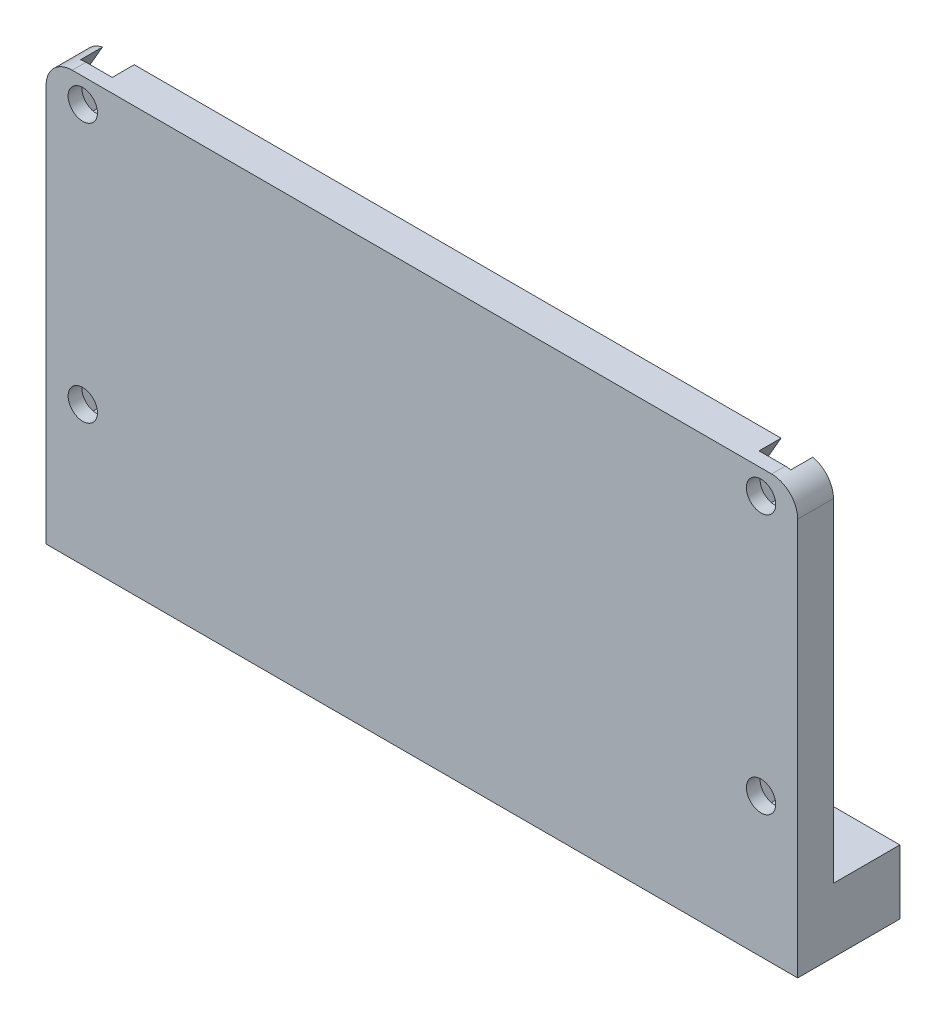
SolidWorks part; units mm, degrees
ref_plane "Front Plane" through (0, 0, 0) normal (0, 0, 1) x (1, 0, 0)
ref_plane "Top Plane" through (0, 0, 0) normal (0, 1, 0) x (1, 0, 0)
ref_plane "Right Plane" through (0, 0, 0) normal (1, 0, 0) x (0, 0, -1)
sketch "Sketch1" plane through (0, 0, 0) normal (0, 0, 1) x (1, 0, 0)
  line L1 (81, 11.6) -> (1, 11.6) construction
  line L3 (0, -35.2) -> (82, -35.2)
  line L5 (79.15, 11.6) -> (2.85, 11.6)
  line L9 (82, -35.2) -> (82, 8.75)
  line L10 (0, 8.75) -> (0, -35.2)
  line L11 (4, 8.9396) -> (4, -41.6656) construction
  circle A0 centre (4, 8.9396) radius 1.6 construction
  circle A1 centre (78, 8.9396) radius 1.6 construction
  circle A2 centre (4, -29.89) radius 1.6 construction
  circle A3 centre (4, 8.9396) radius 1.6
  circle A4 centre (78, 8.9396) radius 1.6
  arc A5 (82, 8.75) -> (79.15, 11.6) centre (79.15, 8.75) ccw
  arc A6 (0, 8.75) -> (2.85, 11.6) centre (2.85, 8.75) cw
  dimension "D1" = 46.8
  dimension "D2" = 2.85
extrude "Boss-Extrude1" add sketch "Sketch1" along normal blind 11.15 contours A3 | L5 A6 L10 L3 L9 A5 | A4 region at (4, 8.9396, 0)
sketch "Sketch2" plane through (0, 0, 0) normal (0, 0, -1) x (-1, 0, 0)
  line L0 (0, -49.6) -> (-82, -49.6) construction
  line L1 (0, -49.6) -> (-82, -49.6) construction
  line L2 (-82, -54.6) -> (0, -54.6)
  line L3 (-82, -34.6) -> (0, -34.6)
  line L4 (-82, -35.2) -> (-82, 8.75) construction
  line L5 (0, 8.75) -> (0, -35.2) construction
  line L7 (0, -34.6) -> (0, -35.2)
  line L8 (-82, -35.2) -> (-82, -34.6)
  line L9 (-82, -35.2) -> (0, -35.2)
  dimension "D1" = 5
  dimension "D2" = 20
extrude "Cut-Extrude1" cut sketch "Sketch2" against normal blind 8 contours L3 L7 L9 L8
sketch "Sketch3" plane through (0, -34.6, 0) normal (0, -1, 0) x (1, 0, 0)
  line L0 (10.85, 4) -> (10.85, 0)
  line L1 (14.15, 4) -> (14.15, 0)
  line L2 (16.75, 4) -> (16.75, 0)
  line L3 (23.25, 4) -> (23.25, 0)
  line L4 (0, 0) -> (82, 0)
  line L5 (82, 0) -> (82, 8)
  line L6 (82, 8) -> (0, 8)
  line L7 (0, 8) -> (0, 0)
  line L8 (10.85, 0) -> (14.15, 0)
  line L9 (82, 0) -> (82, 8)
  line L10 (82, 8) -> (0, 8)
  line L11 (0, 8) -> (0, 0)
  line L12 (25.85, 4) -> (25.85, 0)
  line L13 (29.15, 4) -> (29.15, 0)
  line L14 (25.85, 0) -> (82, 0)
  line L15 (16.75, 0) -> (23.25, 0)
  arc A0 (14.15, 4) -> (10.85, 4) centre (12.5, 4) ccw
  arc A1 (23.25, 4) -> (16.75, 4) centre (20, 4) ccw
  arc A2 (29.15, 4) -> (25.85, 4) centre (27.5, 4) ccw
  line M5 (0, 0) -> (82, 0)
  dimension "D2" = 3.3
  dimension "D3" = 3.3
  dimension "D4" = 15
  dimension "D5" = 7.5
  dimension "D6" = 6.5
  dimension "D7" = 20
  dimension "D1" = 0
extrude "Cut-Extrude2" cut sketch "Sketch3" against normal up to next contours L13 A2 L12 M5 | A0 L0 L8 L1 | A1 L2 L15 L3 region at (27.5, -34.6, 2.6608)
sketch "Sketch4" plane through (0, 11.6, 0) normal (0, 1, 0) x (1, 0, 0)
  line L0 (9.25, -4) -> (9.25, 0)
  line L1 (10.85, 0) -> (2.85, 0) construction
  line L2 (15.75, -4) -> (15.75, 0)
  line L3 (16.75, 0) -> (14.15, 0) construction
  line L4 (15.75, 0) -> (9.25, 0)
  line L5 (24.25, -4) -> (24.25, 0)
  line L6 (25.85, 0) -> (23.25, 0) construction
  line L7 (24.25, 0) -> (30.75, 0)
  line L8 (79.15, 0) -> (29.15, 0) construction
  line L9 (30.75, 0) -> (30.75, -4)
  arc A0 (10.85, -4) -> (14.15, -4) centre (12.5, -4) ccw construction
  arc A1 (25.85, -4) -> (29.15, -4) centre (27.5, -4) ccw construction
  arc A2 (10.85, -4) -> (14.15, -4) centre (12.5, -4) ccw construction
  arc A3 (25.85, -4) -> (29.15, -4) centre (27.5, -4) ccw construction
  arc A4 (9.25, -4) -> (15.75, -4) centre (12.5, -4) ccw
  arc A5 (24.25, -4) -> (30.75, -4) centre (27.5, -4) ccw
  dimension "D1" = 6.5
  dimension "D2" = 6.5
extrude "Cut-Extrude3" cut sketch "Sketch4" against normal offset from surface (40.2 mm away) 6 up to face at (25.25, -34.6, 2.9094)
sketch "Sketch6" plane through (0, 11.6, 0) normal (0, 1, 0) x (1, 0, 0)
  line L0 (15.75, -4) -> (15.75, 0) construction
  line L1 (24.25, 0) -> (24.25, -4) construction
  line L2 (15.75, -4) -> (15.75, 0)
  line L3 (24.25, 0) -> (24.25, -4)
  line L4 (12.5, -7.25) -> (0, -7.25)
  line L5 (0, -11.15) -> (0, 0) construction
  line L6 (0, -7.25) -> (0, 1.0612)
  line L7 (0, 1.0612) -> (15.75, 1.0612)
  line L8 (15.75, 1.0612) -> (15.75, 0)
  line L9 (27.5, -7.25) -> (41, -7.25)
  line L10 (41, -7.25) -> (41, 0)
  line L11 (79.15, 0) -> (30.75, 0) construction
  line L12 (41, 0) -> (24.25, 0)
  arc A0 (9.25, -4) -> (15.75, -4) centre (12.5, -4) ccw construction
  arc A1 (24.25, -4) -> (30.75, -4) centre (27.5, -4) ccw construction
  arc A2 (12.5, -7.25) -> (15.75, -4) centre (12.5, -4) ccw
  arc A3 (24.25, -4) -> (27.5, -7.25) centre (27.5, -4) ccw
  dimension "D1" = 41
extrude "Cut-Extrude5" cut sketch "Sketch6" against normal offset from surface (39.2 mm away) 7 up to face at (25.25, -34.6, 2.9094)
ref_plane "Plane1" through (41, 0, 0) normal (-1, 0, 0) x (0, 0, 1)
mirror "Mirror1" about plane through (41, 0, 0) normal (-1, 0, 0) of "Cut-Extrude5", "Cut-Extrude3", "Cut-Extrude2", "Cut-Extrude1"
sketch "Sketch8" plane through (0, 0, 8) normal (0, 0, -1) x (-1, 0, 0)
  line L4 (-82, -34.6) -> (-82, -35.2)
  line L5 (-82, -35.2) -> (0, -35.2)
  line L6 (0, -35.2) -> (0, -34.6)
  line L7 (0, -34.6) -> (-82, -34.6)
  line L8 (-82, -34.6) -> (-82, -35.2)
  line L9 (-82, -35.2) -> (0, -35.2)
  line L10 (0, -35.2) -> (0, -34.6)
  line L11 (0, -34.6) -> (-82, -34.6)
  dimension "D1" = 0
sketch "Sketch9" plane through (0, 0, 0) normal (-1, 0, 0) x (0, 0, 1)
  line L2 (7.25, 11.6) -> (0, 2.4)
  line L3 (0, 11.6) -> (7.25, 11.6)
sketch "Sketch12" plane through (0, 11.6, 0) normal (0, 1, 0) x (1, 0, 0)
  line L0 (16.75, -4) -> (16.75, 0)
  line L1 (16.75, 0) -> (18, 0)
  line L2 (23.25, 0) -> (23.25, -4)
  line L5 (22, 0) -> (23.25, 0)
  line L6 (58.75, -4) -> (58.75, 0)
  line L7 (58.75, 0) -> (60.05, 0)
  line L8 (65.25, 0) -> (65.25, -4) construction
  line L9 (65.25, 0) -> (65.25, -4)
  line L10 (60.05, 0) -> (60.155, -3.1064)
  line L11 (18, 0) -> (18.11, -3.0846)
  line L12 (63.95, 0) -> (65.25, 0)
  line L13 (22, 0) -> (21.89, -3.0846)
  line L15 (63.95, 0) -> (63.845, -3.1064)
  arc A0 (16.75, -4) -> (23.25, -4) centre (20, -4) ccw construction
  arc A1 (58.75, -4) -> (65.25, -4) centre (62, -4) ccw construction
  arc A2 (16.75, -4) -> (23.25, -4) centre (20, -4) ccw
  arc A3 (58.75, -4) -> (65.25, -4) centre (62, -4) ccw
  arc A4 (18.11, -3.0846) -> (21.89, -3.0846) centre (20, -4) ccw
  arc A5 (60.155, -3.1064) -> (63.845, -3.1064) centre (62, -4) ccw
  dimension "D1" = 1.25
  dimension "D2" = 4.1
  dimension "D3" = 1.3
  dimension "D4" = 1.3
  dimension "D5" = 1.25
extrude "Boss-Extrude2" add sketch "Sketch12" against normal offset from surface (32.2 mm away) 7 up to face at (41, -27.6, 3.9744)
chamfer "Chamfer3" distance 1.1 angle 45 3 edges at (58.75, -20.6, 2) (65.25, -20.6, 2) (62, -20.6, 7.25)
chamfer "Chamfer4" distance 1.1 angle 45 3 edges at (16.75, -20.6, 2) (23.25, -20.6, 2) (20, -20.6, 7.25)
extrude "Cut-Extrude12" cut sketch "Sketch9" against normal through all and the other way through all flip side to cut contours L3 L2
fillet "Fillet3" radius 15 3 edges at (16.875, 2.4, 0) (65.1, 2.4, 0) (58.9, 2.4, 0)
sketch "Sketch13" plane through (0, 0, 7.25) normal (0, 0, -1) x (-1, 0, 0)
  circle A0 centre (-78, 8.9396) radius 2.85
  dimension "D1" = 5.7
sketch "Sketch14" plane through (0, 0, 11.15) normal (0, 0, 1) x (1, 0, 0)
  circle A0 centre (4, -19.4004) radius 1.6 construction
  circle A1 centre (4, -19.4004) radius 1.6
extrude "Cut-Extrude14" cut sketch "Sketch14" against normal through all contours A1
mirror "Mirror3" about plane through (41, 0, 0) normal (-1, 0, 0) of "Cut-Extrude14"
sketch "Sketch18" plane through (0, -27.6, 0) normal (0, 1, 0) x (1, 0, 0)
  line L6 (14.15, 0) -> (14.15, -4)
  line L7 (10.85, -4) -> (10.85, 0)
  line L8 (10.85, 0) -> (9.25, 0)
  line L9 (9.25, 0) -> (9.25, -4)
  line L10 (15.75, -4) -> (15.75, 0)
  line L11 (15.75, 0) -> (14.15, 0)
  line L12 (14.15, 0) -> (14.15, -1.2)
  line L13 (10.85, -1.2) -> (10.85, 0)
  line L14 (10.85, 0) -> (9.25, 0)
  line L15 (9.25, 0) -> (9.25, -4)
  line L16 (15.75, -4) -> (15.75, 0)
  line L17 (15.75, 0) -> (14.15, 0)
  line L18 (29.15, 0) -> (29.15, -4)
  line L19 (25.85, -4) -> (25.85, 0)
  line L20 (25.85, 0) -> (24.25, 0)
  line L21 (24.25, 0) -> (24.25, -4)
  line L22 (30.75, -4) -> (30.75, 0)
  line L23 (30.75, 0) -> (29.15, 0)
  line L24 (29.15, 0) -> (29.15, -1.2)
  line L25 (25.85, -1.2) -> (25.85, 0)
  line L26 (25.85, 0) -> (24.25, 0)
  line L27 (24.25, 0) -> (24.25, -4)
  line L28 (30.75, -4) -> (30.75, 0)
  line L29 (30.75, 0) -> (29.15, 0)
  arc A0 (10.85, -1.2) -> (9.25, -4) centre (12.5, -4) ccw
  arc A1 (15.75, -4) -> (14.15, -1.2) centre (12.5, -4) ccw
  arc A2 (10.85, -4) -> (14.15, -4) centre (12.5, -4) ccw
  arc A3 (9.25, -4) -> (15.75, -4) centre (12.5, -4) ccw
  arc A4 (25.85, -1.2) -> (24.25, -4) centre (27.5, -4) ccw
  arc A5 (30.75, -4) -> (29.15, -1.2) centre (27.5, -4) ccw
  arc A6 (25.85, -4) -> (29.15, -4) centre (27.5, -4) ccw
  arc A7 (24.25, -4) -> (30.75, -4) centre (27.5, -4) ccw
  dimension "D1" = 0
  dimension "D2" = 0
extrude "Boss-Extrude3" add sketch "Sketch18" against normal blind 3.5
mirror "Mirror5" about plane through (41, 0, 0) normal (-1, 0, 0) of "Boss-Extrude3"
sketch "Sketch19" plane through (0, 0, 7.25) normal (0, 0, -1) x (-1, 0, 0)
  circle A0 centre (-78, -19.4004) radius 2.85
extrude "Cut-Extrude16" cut sketch "Sketch8" against normal through all contours L11 L8 L9 L10
sketch "Sketch20" plane through (0, 0, 7.25) normal (0, 0, -1) x (-1, 0, 0)
  line L1 (-76.375, 11.7542) -> (-79.625, 11.7542)
  line L2 (-79.625, 11.7542) -> (-81.25, 8.9396)
  line L3 (-81.25, 8.9396) -> (-79.625, 6.1251)
  line L4 (-79.625, 6.1251) -> (-76.375, 6.1251)
  line L5 (-76.375, 6.1251) -> (-74.75, 8.9396)
  line L6 (-74.75, 8.9396) -> (-76.375, 11.7542)
  line L7 (-79.625, -16.5858) -> (-81.25, -19.4004)
  line L8 (-81.25, -19.4004) -> (-79.625, -22.2149)
  line L9 (-79.625, -22.2149) -> (-76.375, -22.2149)
  line L10 (-76.375, -22.2149) -> (-74.75, -19.4004)
  line L11 (-74.75, -19.4004) -> (-76.375, -16.5858)
  line L12 (-76.375, -16.5858) -> (-79.625, -16.5858)
  circle A0 centre (-78, 8.9396) radius 3.25 construction
  circle A2 centre (-78, -19.4004) radius 3.25 construction
  dimension "D1" = 6.5
  dimension "D2" = 6.5
extrude "Cut-Extrude17" cut sketch "Sketch20" against normal blind 2.4
mirror "Mirror7" about plane through (41, 0, 0) normal (-1, 0, 0) of "Cut-Extrude17"
